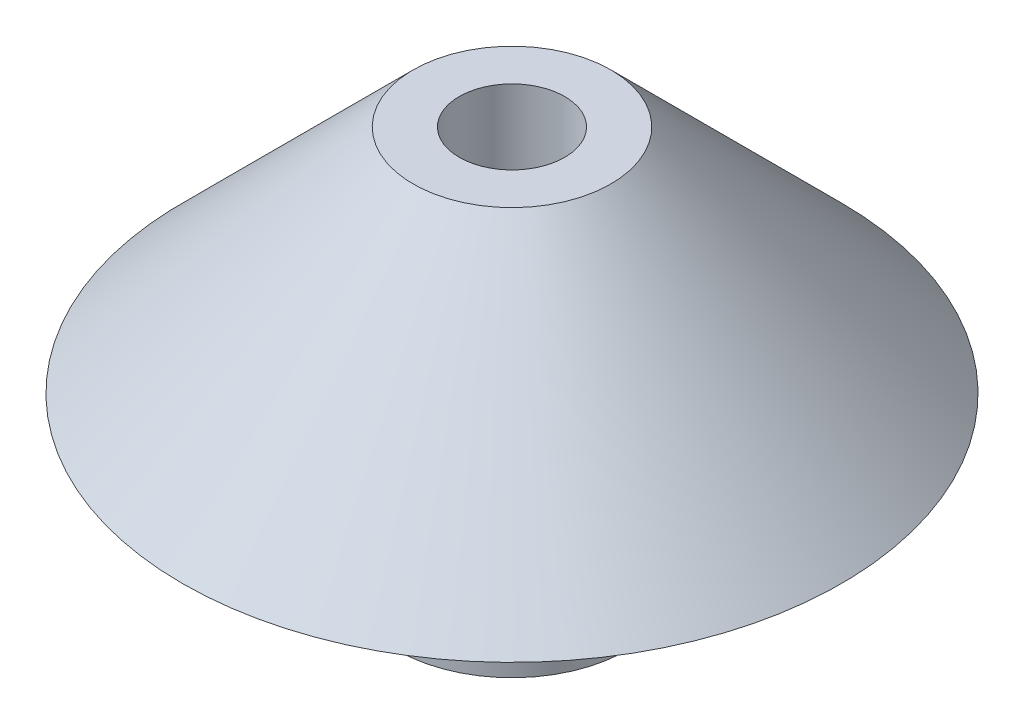
SolidWorks part; units mm, degrees
ref_plane "Front Plane" through (0, 0, 0) normal (0, 0, 1) x (1, 0, 0)
ref_plane "Top Plane" through (0, 0, 0) normal (0, 1, 0) x (1, 0, 0)
ref_plane "Right Plane" through (0, 0, 0) normal (1, 0, 0) x (0, 0, -1)
sketch "Sketch1" plane through (0, 0, 0) normal (0, 1, 0) x (1, 0, 0)
  circle A0 centre (0, 0) radius 10
extrude "Boss-Extrude1" add sketch "Sketch1" along normal blind 7
chamfer "Chamfer1" distance 7 angle 45 1 edges at (0, 7, 10)
sketch "Sketch5" plane through (0, 0, 0) normal (0, 0, 1) x (1, 0, 0)
  line L0 (0, 0) -> (0, 10) construction
sketch "Sketch6" plane through (0, 0, 0) normal (0, 0, 1) x (1, 0, 0)
  line L0 (10, 0) -> (0, 10) construction
sketch "Sketch9" plane through (0, 7, 0) normal (0, 1, 0) x (1, 0, 0)
  line L0 (0, 0) -> (0, -3) construction
  circle A0 centre (0, 0) radius 3 construction
ref_plane "Plane1" through (0, 0, 0) normal (0, 0, 1) x (1, 0, 0)
sketch "Sketch10" plane through (0, 0, 0) normal (0, -1, 0) x (1, 0, 0)
  circle A0 centre (0, 0) radius 3.5
  dimension "D1" = 7
extrude "Boss-Extrude2" add sketch "Sketch10" along normal blind 5
sketch "Sketch2" plane through (0, 7, 0) normal (0, 1, 0) x (1, 0, 0)
  circle A0 centre (0, 0) radius 1.6
  dimension "D1" = 3.2
extrude "Cut-Extrude1" cut sketch "Sketch2" against normal through all
sketch "Sketch11" plane through (0, 0, 0) normal (0, 0, 1) x (1, 0, 0)
  line L0 (-3.5, -5) -> (3.5, -5) construction
  circle A0 centre (0, -2.5) radius 0.8
  dimension "D1" = 1.6
  dimension "D2" = 2.5
extrude "Cut-Extrude2" cut sketch "Sketch11" against normal through all
